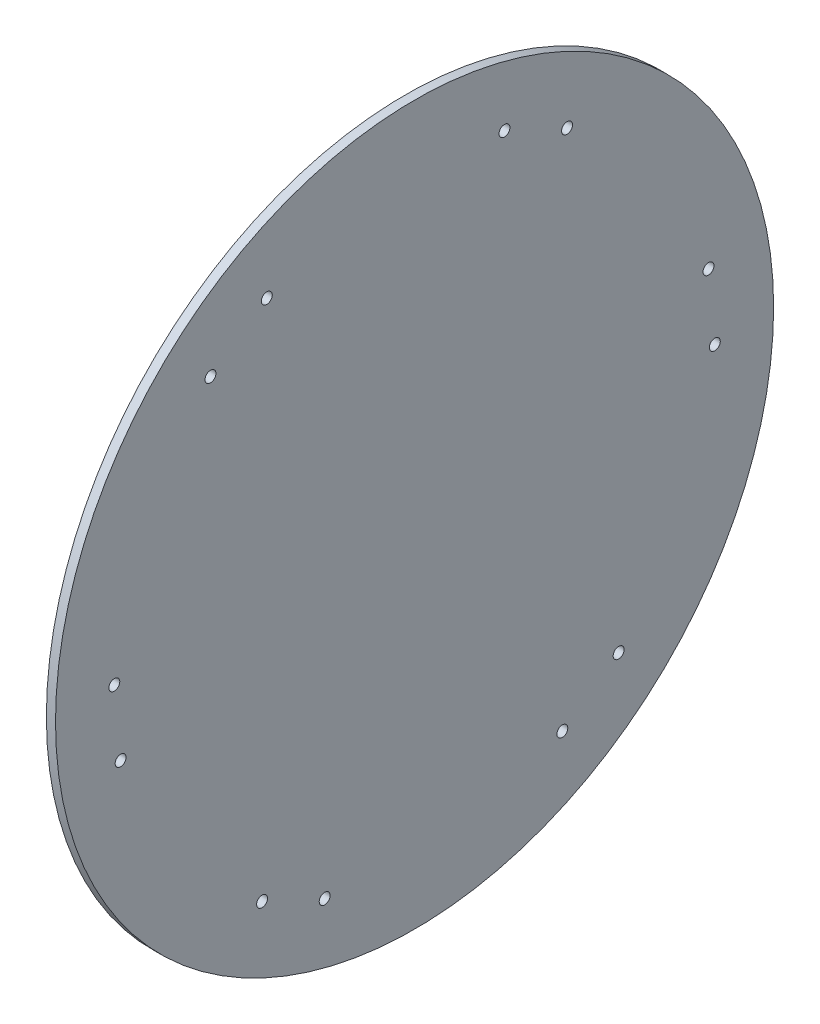
SolidWorks part; units mm, degrees
material "Oak"
ref_plane "Front Plane" through (0, 0, 0) normal (0, 0, 1) x (1, 0, 0)
ref_plane "Top Plane" through (0, 0, 0) normal (0, 1, 0) x (1, 0, 0)
ref_plane "Right Plane" through (0, 0, 0) normal (1, 0, 0) x (0, 0, -1)
sketch "Sketch2" plane through (0, 0, 0) normal (1, 0, 0) x (0, 0, -1)
  circle A0 centre (0, 0) radius 125
  dimension "D1" = 250
extrude "Boss-Extrude1" add sketch "Sketch2" along normal blind 3.18
sketch "Sketch3" plane through (0, 0, 0) normal (-1, 0, 0) x (0, 0, 1)
  circle A5 centre (104.5235, 0.9499) radius 1.9
  circle A12 centre (102.3318, -22.9498) radius 1.9
  circle A13 centre (31.2908, -100.0969) radius 1.9
  circle A14 centre (53.0844, -90.045) radius 1.9
  circle A15 centre (-51.4391, -90.9949) radius 1.9
  circle A16 centre (-71.041, -77.147) radius 1.9
  circle A17 centre (-102.3318, 22.9498) radius 1.9
  circle A18 centre (-104.5235, -0.9499) radius 1.9
  circle A19 centre (-53.0844, 90.045) radius 1.9
  circle A20 centre (-31.2908, 100.0969) radius 1.9
  circle A21 centre (51.4391, 90.9949) radius 1.9
  circle A22 centre (71.041, 77.147) radius 1.9
  dimension "D1" = 3.8
extrude "Cut-Extrude1" cut sketch "Sketch3" against normal through all
sketch "Sketch4" plane through (3.18, 0, 0) normal (1, 0, 0) x (0, 0, -1)
  line L0 (72.2937, 101.9736) -> (-72.2937, -101.9736) construction
  circle A0 centre (0, 0) radius 125 construction
